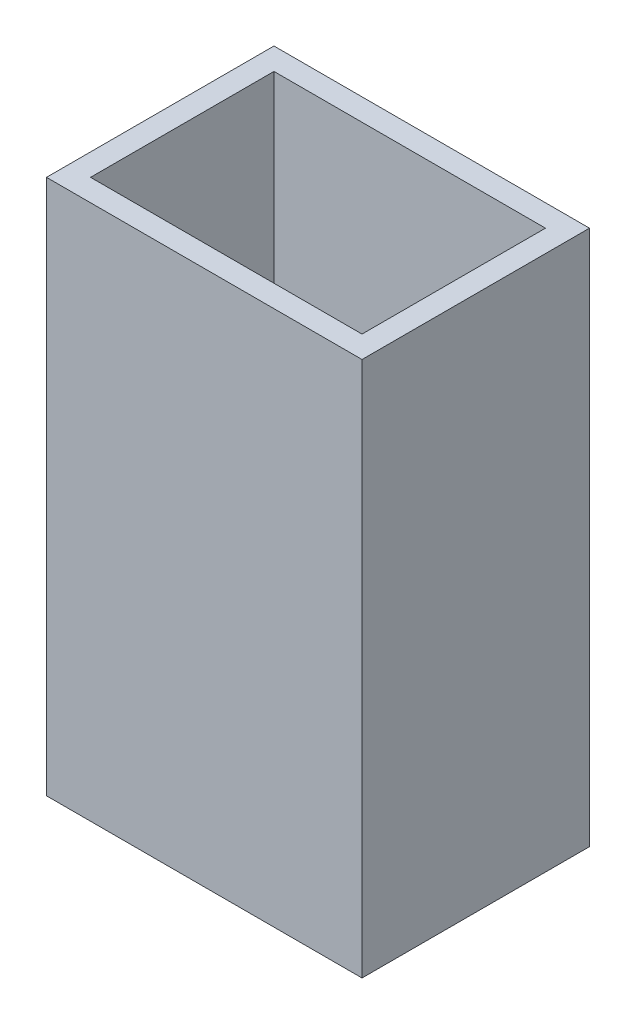
SolidWorks part; units mm, degrees
ref_plane "Front Plane" through (0, 0, 0) normal (0, 0, 1) x (1, 0, 0)
ref_plane "Top Plane" through (0, 0, 0) normal (0, 1, 0) x (1, 0, 0)
ref_plane "Right Plane" through (0, 0, 0) normal (1, 0, 0) x (0, 0, -1)
sketch "Sketch1" plane through (0, 0, 0) normal (0, 1, 0) x (1, 0, 0)
  line L1 (-18.5, -12.5) -> (18.5, -12.5)
  line L2 (-18.5, -12.5) -> (-18.5, 12.5)
  line L3 (-18.5, 12.5) -> (18.5, 12.5)
  line L4 (18.5, -12.5) -> (18.5, 12.5)
  line L5 (-18.5, -12.5) -> (18.5, 12.5) construction
  line L6 (-18.5, 12.5) -> (18.5, -12.5) construction
  line L7 (-21.5, -15.5) -> (21.5, -15.5)
  line L8 (-21.5, -15.5) -> (-21.5, 15.5)
  line L9 (-21.5, 15.5) -> (21.5, 15.5)
  line L10 (21.5, -15.5) -> (21.5, 15.5)
  line L11 (-21.5, -15.5) -> (21.5, 15.5) construction
  line L12 (-21.5, 15.5) -> (21.5, -15.5) construction
  point P0 (0, 0)
  point P6 (0, 0)
  dimension "D1" = 25
  dimension "D2" = 37
  dimension "D3" = 3
  dimension "D4" = 3
extrude "Boss-Extrude1" add sketch "Sketch1" along normal blind 3 contours L7 L10 L9 L8
extrude "Boss-Extrude2" add sketch "Sketch1<3>" along normal blind 70 from surface starting at face at (0, 3, 0)
sketch "Sketch1<3>" plane through (0, 0, 0) normal (0, 1, 0) x (1, 0, 0) same geometry as "Sketch1"
sketch "Sketch2" plane through (0, 3, 0) normal (0, 1, 0) x (1, 0, 0)
  line L1 (-12.5, -9.5) -> (12.5, -9.5) construction
  line L2 (-12.5, -9.5) -> (-12.5, 9.5) construction
  line L3 (-12.5, 9.5) -> (12.5, 9.5) construction
  line L4 (12.5, -9.5) -> (12.5, 9.5) construction
  line L5 (-12.5, -9.5) -> (12.5, 9.5) construction
  line L6 (-12.5, 9.5) -> (12.5, -9.5) construction
  point P0 (0, 0)
  dimension "D1" = 25
  dimension "D2" = 19
hole_wizard "M3 Clearance Hole1" positions "Sketch3" profile "Sketch4" hole size "M3" standard "ISO" end condition through all
sketch "Sketch3" plane through (0, 3, 0) normal (0, 1, 0) x (1, 0, 0)
  point P0 (-12.5, 9.5)
  point P3 (12.5, 9.5)
  point P6 (12.5, -9.5)
  point P9 (-12.5, -9.5)
sketch "Sketch4" plane through (-12.5, 3, -9.5) normal (1, 0, 0) x (0, 0, 1)
  line L0 (0, 0) -> (0, 3)
  line L1 (0, 3) -> (1.7, 3)
  line L2 (1.7, 3) -> (1.7, 0)
  line L5 (1.7, 0) -> (0, 0)
  line L11 (0, -6.35) -> (0, 107.95) construction
  dimension "Thru Hole Dia." = 3.4
  dimension "Thru Hole Depth" = 3
